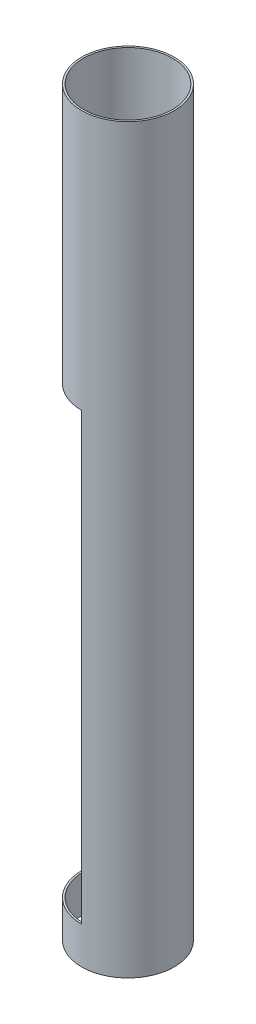
SolidWorks part; units mm, degrees
ref_plane "Plan de face" through (0, 0, 0) normal (0, 0, 1) x (1, 0, 0)
ref_plane "Plan de dessus" through (0, 0, 0) normal (0, 1, 0) x (1, 0, 0)
ref_plane "Plan de droite" through (0, 0, 0) normal (1, 0, 0) x (0, 0, -1)
sketch "Esquisse1" plane through (0, 0, 0) normal (0, 1, 0) x (1, 0, 0)
  circle A0 centre (0, 0) radius 25
extrude "Boss.-Extru.1" add sketch "Esquisse1" against normal blind 200 and the other way blind 200
sketch "Esquisse2" plane through (0, 200, 0) normal (0, 1, 0) x (1, 0, 0)
  circle A0 centre (0, 0) radius 24
  dimension "D1" = 48
extrude "Enlèv. mat.-Extru.1" cut sketch "Esquisse2" against normal blind 400
sketch "Esquisse3" plane through (0, 0, 0) normal (0, 1, 0) x (1, 0, 0)
  line L1 (0, 300) -> (-240, 300)
  line L2 (0, 300) -> (0, -300)
  line L3 (0, -300) -> (-240, -300)
  line L4 (-240, 300) -> (-240, -300)
  dimension "D1" = 240
  dimension "D2" = 300
  dimension "D3" = 600
extrude "Enlèv. mat.-Extru.2" cut sketch "Esquisse3" against normal blind 180 and the other way blind 60
